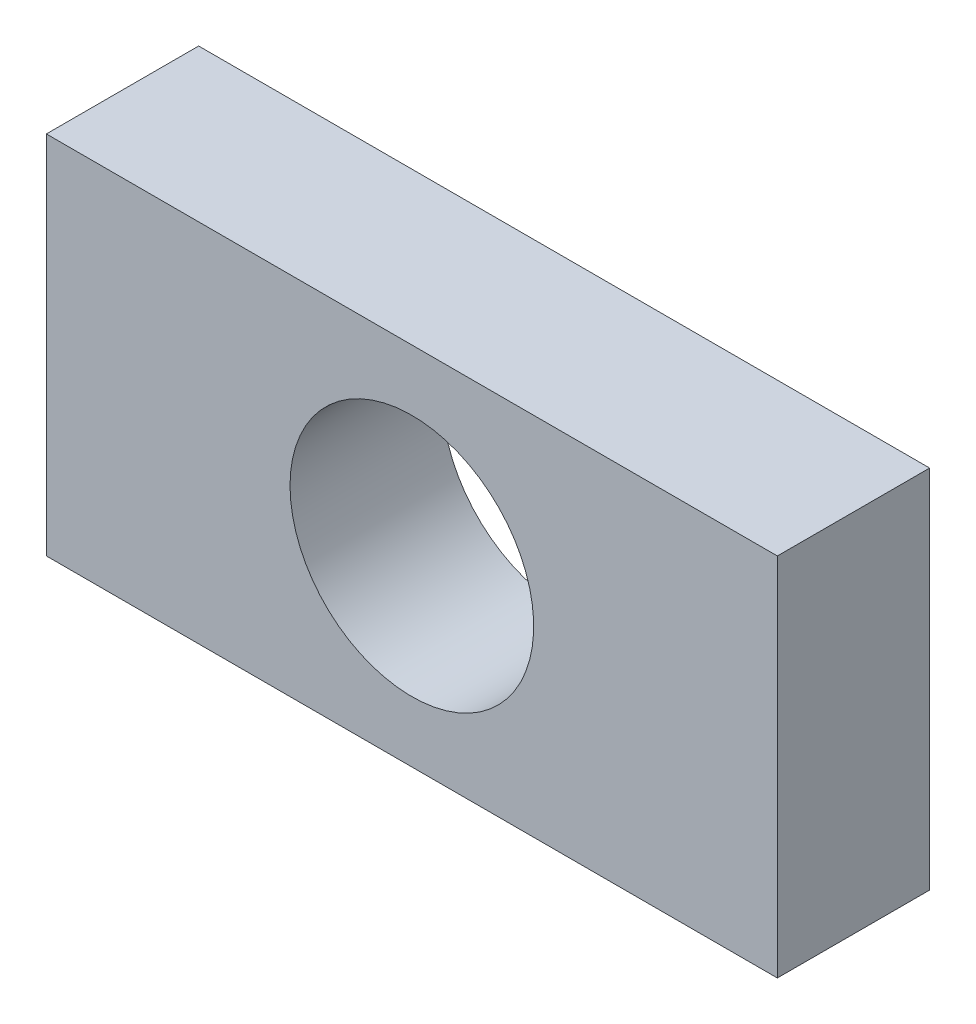
SolidWorks part; units mm, degrees
ref_plane "Front Plane" through (0, 0, 0) normal (0, 0, 1) x (1, 0, 0)
ref_plane "Top Plane" through (0, 0, 0) normal (0, 1, 0) x (1, 0, 0)
ref_plane "Right Plane" through (0, 0, 0) normal (1, 0, 0) x (0, 0, -1)
sketch "Sketch1" plane through (0, 0, 0) normal (0, 0, 1) x (1, 0, 0)
  line L1 (0, 0) -> (152.4, 0)
  line L2 (0, 0) -> (0, 76.2)
  line L3 (0, 76.2) -> (152.4, 76.2)
  line L4 (152.4, 0) -> (152.4, 76.2)
  dimension "D1" = 152.4
  dimension "D2" = 76.2
extrude "Boss-Extrude1" add sketch "Sketch1" along normal blind 31.75
sketch "Sketch2" plane through (0, 0, 0) normal (0, 0, -1) x (-1, 0, 0)
  line L0 (0, 38.1) -> (-152.4, 38.1) construction
  line L1 (0, 76.2) -> (0, 0) construction
  line L2 (-152.4, 0) -> (-152.4, 76.2) construction
  line L4 (-152.4, 76.2) -> (0, 76.2) construction
  line L5 (-76.2, 76.2) -> (-76.2, 0) construction
  line L6 (0, 0) -> (-152.4, 0) construction
  circle A0 centre (-76.2, 38.1) radius 25.4
  dimension "D1" = 50.8
extrude "Cut-Extrude1" cut sketch "Sketch2" against normal through all
